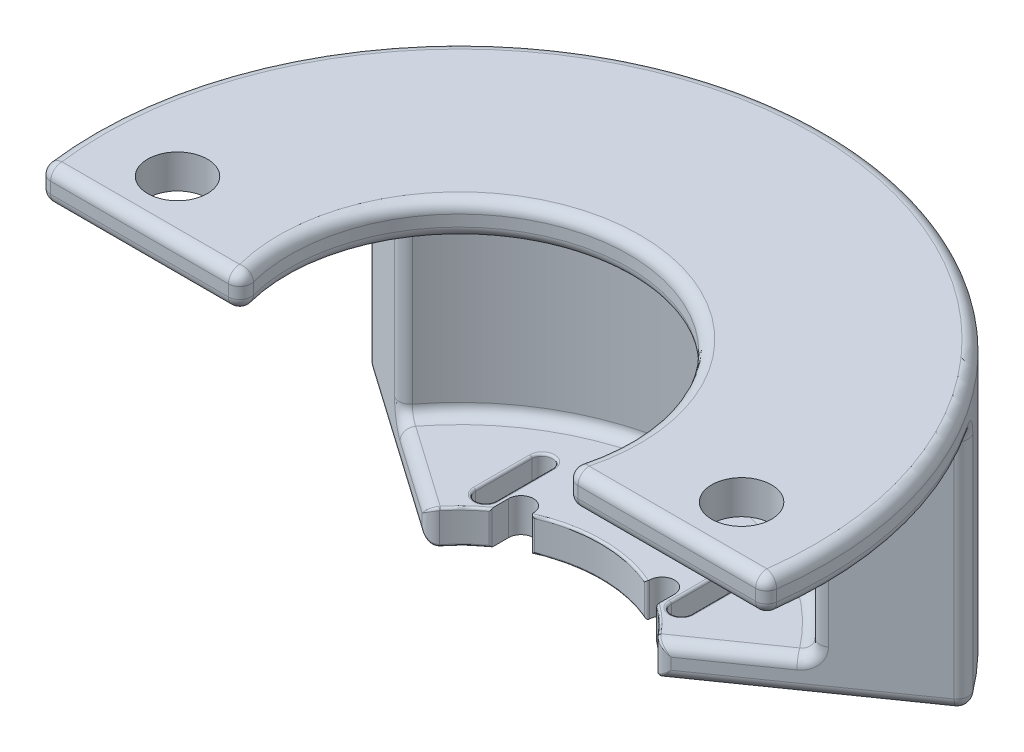
SolidWorks part; units mm, degrees
ref_plane "Front" through (0, 0, 0) normal (0, 0, 1) x (1, 0, 0)
ref_plane "Top" through (0, 0, 0) normal (0, 1, 0) x (1, 0, 0)
ref_plane "Right" through (0, 0, 0) normal (1, 0, 0) x (0, 0, -1)
sketch "Sketch1" plane through (0, 0, 0) normal (0, 1, 0) x (1, 0, 0)
  circle A0 centre (0, 0) radius 32.5
  circle A1 centre (0, 0) radius 15
  dimension "D1" = 30
  dimension "D2" = 65
extrude "Boss-Extrude1" add sketch "Sketch1" along normal blind 3
hole_wizard "M5 Clearance Hole1" positions "Sketch2" profile "Sketch3" hole size "M5" standard "ISO"
sketch "Sketch2" plane through (0, 3, 0) normal (0, 1, 0) x (1, 0, 0)
  line L0 (25, 0) -> (-25, 0) construction
  point P0 (25, 0)
  point P2 (-25, 0)
  dimension "D1" = 50
sketch "Sketch3" plane through (25, 3, 0) normal (1, 0, 0) x (0, 0, 1)
  line L0 (0, 0) -> (0, 11.6923)
  line L1 (0, 11.6923) -> (2.65, 10.1)
  line L2 (2.65, 10.1) -> (2.65, 0)
  line L5 (2.65, 0) -> (0, 0)
  line L10 (0, 11.6923) -> (-2.65, 10.1) construction
  line L11 (0, -6.35) -> (0, 107.95) construction
  dimension "Hole Dia." = 5.3
  dimension "Hole Depth" = 10.1
  dimension "Drill Angle" = 118
sketch "Sketch4" plane through (0, 0, 0) normal (0, -1, 0) x (1, 0, 0)
  line L1 (-36.5255, 5) -> (40.3726, 5)
  line L2 (-36.5255, 5) -> (-36.5255, 38.2404)
  line L3 (-36.5255, 38.2404) -> (40.3726, 38.2404)
  line L4 (40.3726, 5) -> (40.3726, 38.2404)
  dimension "D1" = 5
extrude "Cut-Extrude1" cut sketch "Sketch4" against normal through all
sketch "Sketch9" plane through (0, 0, 0) normal (0, -1, 0) x (1, 0, 0)
  line L0 (-18.4309, -12.9055) -> (-26.6224, -18.6412)
  line L1 (0, 15.3648) -> (0, -49.7612) construction
  line L2 (0, 0) -> (-18.4309, -12.9055) construction
  line L3 (18.4309, -12.9055) -> (26.6224, -18.6412)
  arc A0 (-32.1131, 5) -> (32.1131, 5) centre (0, 0) ccw construction
  arc A1 (-26.6224, -18.6412) -> (26.6224, -18.6412) centre (0, 0) ccw
  arc A2 (-18.4309, -12.9055) -> (18.4309, -12.9055) centre (0, 0) ccw
  dimension "D2" = 10
  dimension "D1" = 55
extrude "Boss-Extrude3" add sketch "Sketch9" along normal blind 21.76
sketch "Sketch10" plane through (0, -21.76, 0) normal (0, -1, 0) x (1, 0, 0)
  line L0 (0, -34.1752) -> (0, 13.1156) construction
  line L1 (-18.4309, -12.9055) -> (-10.2394, -7.1697)
  line L2 (18.4309, -12.9055) -> (10.2394, -7.1697)
  line L3 (26.6224, -18.6412) -> (18.4309, -12.9055)
  line L4 (-18.4309, -12.9055) -> (-26.6224, -18.6412)
  line L5 (26.6224, -18.6412) -> (18.4309, -12.9055)
  line L6 (-18.4309, -12.9055) -> (-26.6224, -18.6412)
  arc A0 (-18.4309, -12.9055) -> (18.4309, -12.9055) centre (0, 0) ccw construction
  arc A1 (-10.2394, -7.1697) -> (10.2394, -7.1697) centre (0, 0) ccw
  arc A3 (-26.6224, -18.6412) -> (26.6224, -18.6412) centre (0, 0) ccw
  arc A4 (-18.4309, -12.9055) -> (18.4309, -12.9055) centre (0, 0) ccw
  arc A5 (-26.6224, -18.6412) -> (26.6224, -18.6412) centre (0, 0) ccw
  dimension "D2" = 10
  dimension "D1" = 0
extrude "Boss-Extrude4" add sketch "Sketch10" against normal blind 3
sketch "Sketch11" plane through (0, -21.76, 0) normal (0, -1, 0) x (1, 0, 0)
  line L0 (0, 0) -> (0, -46.1012) construction
  line L1 (-8.675, -16) -> (-8.675, -11) construction
  line L2 (-9.575, -16) -> (-9.575, -11)
  line L3 (-7.775, -16) -> (-7.775, -11)
  line L4 (8.675, -16) -> (8.675, -11) construction
  line L5 (9.575, -16) -> (9.575, -11)
  line L6 (7.775, -16) -> (7.775, -11)
  line L7 (-6.25, -11.7) -> (-6.25, -8.7) construction
  line L8 (-7.35, -11.7) -> (-7.35, -8.7)
  line L9 (-5.15, -11.7) -> (-5.15, -8.7)
  line L10 (6.25, -11.7) -> (6.25, -8.7) construction
  line L11 (7.35, -11.7) -> (7.35, -8.7)
  line L12 (5.15, -11.7) -> (5.15, -8.7)
  arc A0 (-9.575, -16) -> (-7.775, -16) centre (-8.675, -16) ccw
  arc A1 (-7.775, -11) -> (-9.575, -11) centre (-8.675, -11) ccw
  arc A2 (9.575, -16) -> (7.775, -16) centre (8.675, -16) cw
  arc A3 (7.775, -11) -> (9.575, -11) centre (8.675, -11) cw
  arc A4 (-7.35, -11.7) -> (-5.15, -11.7) centre (-6.25, -11.7) ccw
  arc A5 (-5.15, -8.7) -> (-7.35, -8.7) centre (-6.25, -8.7) ccw
  arc A7 (7.35, -11.7) -> (5.15, -11.7) centre (6.25, -11.7) cw
  arc A8 (5.15, -8.7) -> (7.35, -8.7) centre (6.25, -8.7) cw
  point P6 (-8.675, -13.5)
  point P13 (8.675, -13.5)
  point P20 (-6.25, -10.2)
  point P27 (6.25, -10.2)
  dimension "D1" = 0.9
  dimension "D5" = 1.1
  dimension "D2" = 5
  dimension "D3" = 19.15
  dimension "D4" = 11
  dimension "D6" = 14.7
  dimension "D7" = 3
  dimension "D8" = 10.2
extrude "Cut-Extrude2" cut sketch "Sketch11" against normal up to next
fillet "Fillet1" radius 1 28 edges at (-22.5267, 0, -15.7734) (-14.3352, -18.76, -10.0376) (-10.2394, -20.26, -7.1697) (-18.4309, -21.76, -12.9055) (18.4309, -21.76, -12.9055) (10.2394, -20.26, -7.1697) (14.3352, -18.76, -10.0376) (22.5267, 0, -15.7734) (-18.4309, -9.38, -12.9055) (0, 0, -22.5) (18.4309, -9.38, -12.9055) (0, -18.76, -22.5) (23.1276, 0, 5) (23.1276, 3, 5) (0, -21.76, -32.5) (26.6224, -10.88, -18.6412) (31.6574, 0, -7.3524) (32.1131, 1.5, 5) (0, 3, -32.5) (-31.6574, 0, -7.3524) (-26.6224, -10.88, -18.6412) (-32.1131, 1.5, 5) (-23.1276, 3, 5) (-23.1276, 0, 5) (0, 0, -15) (-14.1421, 1.5, 5) (0, 3, -15) (14.1421, 1.5, 5)
fillet "Fillet2" radius 0.2 34 edges at (10.3176, -19.0796, -7.5506) (10.3176, -21.4404, -7.5506) (-10.3176, -21.4404, -7.5506) (-10.3176, -19.0796, -7.5506) (8.675, -18.76, -16.9) (9.575, -18.76, -13.5) (8.675, -18.76, -10.1) (-9.575, -18.76, -13.5) (-8.675, -18.76, -16.9) (-7.775, -18.76, -13.5) (-8.675, -21.76, -16.9) (-9.575, -21.76, -13.5) (-8.675, -21.76, -10.1) (8.675, -21.76, -10.1) (9.575, -21.76, -13.5) (8.675, -21.76, -16.9) (7.35, -20.26, -10.1108) (8.559, -18.76, -9.1101) (8.559, -21.76, -9.1101) (0, -21.76, -12.5) (-5.15, -20.26, -11.3898) (0, -18.76, -12.5) (5.15, -20.26, -11.3898) (-7.35, -20.26, -10.1108) (-8.559, -21.76, -9.1101) (-8.559, -18.76, -9.1101) (7.775, -18.76, -13.5) (-8.675, -18.76, -10.1) (-7.775, -21.76, -13.5) (7.775, -21.76, -13.5)
